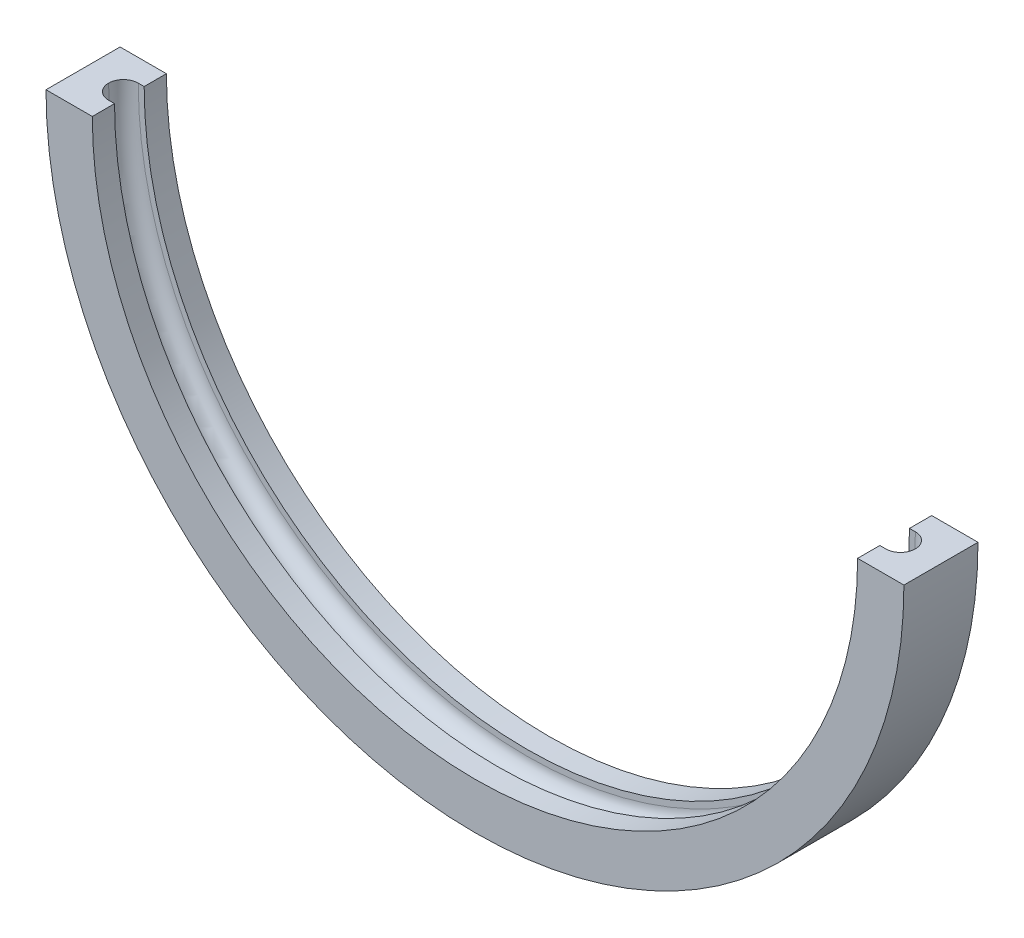
SolidWorks part; units mm, degrees
ref_plane "Front Plane" through (0, 0, 0) normal (0, 0, 1) x (1, 0, 0)
ref_plane "Top Plane" through (0, 0, 0) normal (0, 1, 0) x (1, 0, 0)
ref_plane "Right Plane" through (0, 0, 0) normal (1, 0, 0) x (0, 0, -1)
sketch "Sketch1" plane through (0, 0, 0) normal (0, 0, 1) x (1, 0, 0)
  line L0 (-69.1515, 73.533) -> (-73.533, 73.533)
  line L1 (69.1515, 73.533) -> (73.533, 73.533)
  circle A0 centre (0, 73.533) radius 73.533
  circle A1 centre (0, 73.533) radius 69.1515
  dimension "D1" = 147.066
  dimension "D2" = 138.303
extrude "Boss-Extrude1" add sketch "Sketch1" along normal blind 5.08 contours A1 L0 A0 L1 region at (0, 2.7373, 0)
sketch "Sketch3" plane through (0, 0, 5.08) normal (0, 0, 1) x (1, 0, 0)
  line L0 (-65.5955, 73.533) -> (-73.533, 73.533)
  line L1 (65.5955, 73.533) -> (73.533, 73.533)
  circle A0 centre (0, 73.533) radius 73.533
  circle A1 centre (0, 73.533) radius 65.5955
  arc M3 (69.1515, 73.533) -> (-69.1515, 73.533) centre (0, 73.533) cw
  line M4 (-69.1515, 73.533) -> (-73.533, 73.533)
  arc M5 (-73.533, 73.533) -> (73.533, 73.533) centre (0, 73.533) ccw
  line M6 (73.533, 73.533) -> (69.1515, 73.533)
  dimension "D1" = 131.191
extrude "Boss-Extrude2" add sketch "Sketch3" along normal blind 3.81 contours A1 L0 L1 M3 | M6 M3 M4 M5 region at (0, 6.3912, 5.08) region at (0, 2.7373, 5.08)
sketch "Sketch4" plane through (0, 0, 0) normal (0, 0, -1) x (-1, 0, 0)
  line L0 (-65.5955, 73.533) -> (-73.533, 73.533)
  line L1 (65.5955, 73.533) -> (73.533, 73.533)
  circle A0 centre (0, 73.533) radius 73.533
  circle A1 centre (0, 73.533) radius 65.5955
  arc M3 (69.1515, 73.533) -> (-69.1515, 73.533) centre (0, 73.533) cw
  line M4 (-69.1515, 73.533) -> (-73.533, 73.533)
  arc M5 (-73.533, 73.533) -> (73.533, 73.533) centre (0, 73.533) ccw
  line M6 (73.533, 73.533) -> (69.1515, 73.533)
extrude "Boss-Extrude3" add sketch "Sketch4" along normal blind 3.81 contours A1 L0 L1 M3 | M6 M3 M4 M5 region at (0, 6.3912, 0) region at (0, 2.7373, 0)
fillet "Fillet1" radius 2.54 2 edges at (0, 4.3815, 5.08) (0, 4.3815, 0)
sketch "Sketch5" plane through (0, 0, 0) normal (0, 1, 0) x (1, 0, 0)
  line L0 (69.1515, -2.54) -> (-69.1515, -2.54) construction
  circle A0 centre (0, -2.54) radius 1.524
  dimension "D1" = 3.048
extrude "Cut-Extrude1" [suppressed] cut sketch "Sketch5" along normal blind 6.35
